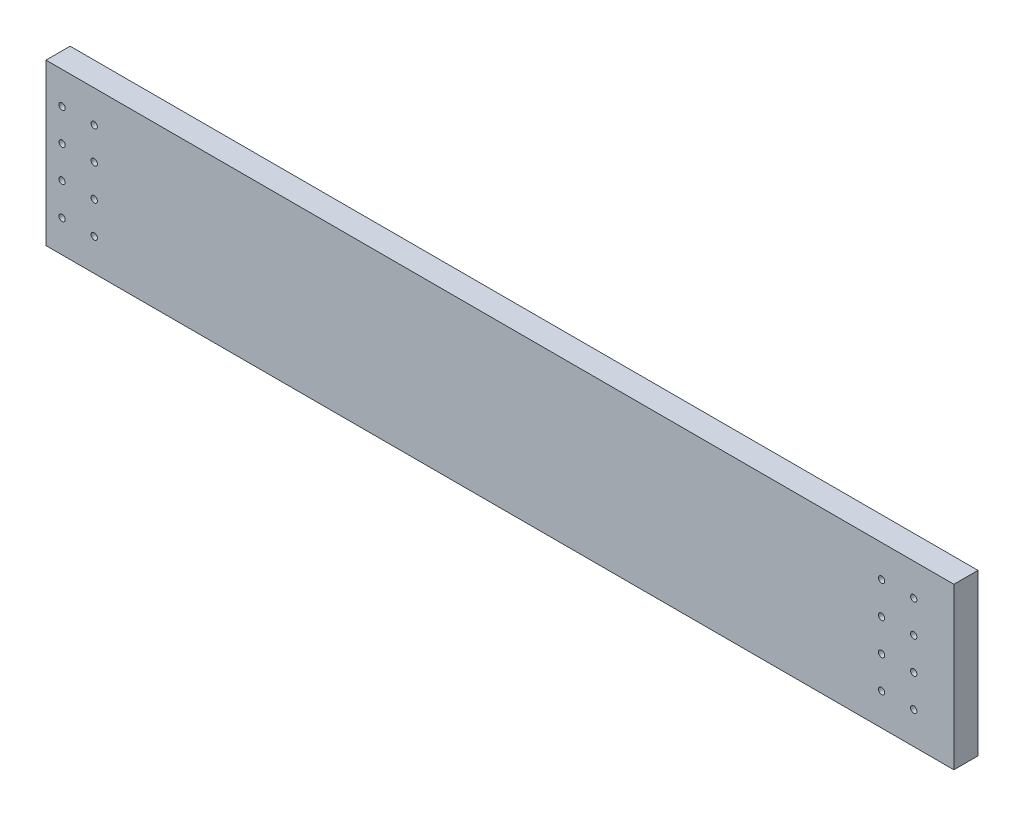
SolidWorks part; units mm, degrees
material "Pine"
ref_plane "Front Plane" through (0, 0, 0) normal (0, 0, 1) x (1, 0, 0)
ref_plane "Top Plane" through (0, 0, 0) normal (0, 1, 0) x (1, 0, 0)
ref_plane "Right Plane" through (0, 0, 0) normal (1, 0, 0) x (0, 0, -1)
sketch "Sketch1" plane through (0, 0, 0) normal (0, 0, 1) x (1, 0, 0)
  line L1 (0, 0) -> (717.55, 0)
  line L2 (0, 0) -> (0, 127)
  line L3 (0, 127) -> (717.55, 127)
  line L4 (717.55, 0) -> (717.55, 127)
  dimension "D1" = 717.55
  dimension "D2" = 127
extrude "Boss-Extrude1" add sketch "Sketch1" along normal blind 19.05
sketch "Sketch2" plane through (0, 0, 19.05) normal (0, 0, 1) x (1, 0, 0)
  line L0 (717.55, 127) -> (0, 127) construction
  line L1 (0, 127) -> (0, 0) construction
  line L2 (717.55, 0) -> (717.55, 127) construction
  circle A0 centre (12.7, 101.6) radius 2.4892
  circle A1 centre (38.1, 101.6) radius 2.4892
  circle A2 centre (38.1, 76.2) radius 2.4892
  circle A3 centre (38.1, 50.8) radius 2.4892
  circle A4 centre (38.1, 25.4) radius 2.4892
  circle A5 centre (12.7, 76.2) radius 2.4892
  circle A6 centre (12.7, 50.8) radius 2.4892
  circle A7 centre (12.7, 25.4) radius 2.4892
  circle A8 centre (685.8, 101.6) radius 2.4892
  circle A9 centre (660.4, 101.6) radius 2.4892
  circle A10 centre (660.4, 76.2) radius 2.4892
  circle A11 centre (660.4, 50.8) radius 2.4892
  circle A12 centre (660.4, 25.4) radius 2.4892
  circle A13 centre (685.8, 76.2) radius 2.4892
  circle A14 centre (685.8, 50.8) radius 2.4892
  circle A15 centre (685.8, 25.4) radius 2.4892
  point P24 (0, 0)
  point P25 (0, 0)
  dimension "D1" = 4.9784
  dimension "D2" = 25.4
  dimension "D3" = 12.7
  dimension "D6" = 31.75
  dimension "D7" = 25.4
  dimension "D8" = 4.9784
  dimension "D11" = 25.4
  dimension "D12" = 25.4
  dimension "D13" = 25.4
  dimension "D14" = 25.4
  dimension "D4" = 2
  dimension "D5" = 4
  dimension "D9" = 2
  dimension "D10" = 4
extrude "Cut-Extrude1" cut sketch "Sketch2" against normal blind 25.4
